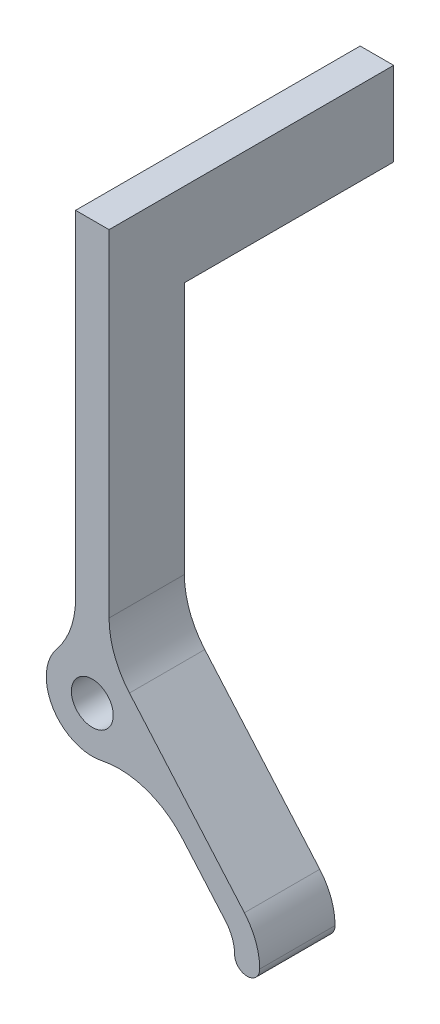
SolidWorks part; units mm, degrees
ref_plane "Front Plane" through (0, 0, 0) normal (0, 0, 1) x (1, 0, 0)
ref_plane "Top Plane" through (0, 0, 0) normal (0, 1, 0) x (1, 0, 0)
ref_plane "Right Plane" through (0, 0, 0) normal (1, 0, 0) x (0, 0, -1)
sketch "Sketch1" plane through (0, 0, 0) normal (0, 0, 1) x (1, 0, 0)
  line L0 (4.1588, 3.5992) -> (18.1711, -12.592)
  line L2 (15.9027, -14.5552) -> (5.0962, -2.0684)
  line L3 (2, 5.1235) -> (2, 50)
  line L4 (2, 50) -> (-2, 50)
  line L5 (-2, 50) -> (-2, 5.1235)
  circle A0 centre (0, 0) radius 2.5
  arc A1 (4.1588, 3.5992) -> (2, 5.1235) centre (0, 0) ccw
  arc A2 (-2, 5.1235) -> (5.0962, -2.0684) centre (0, 0) ccw
  arc A4 (15.9027, -14.5552) -> (17, -17.5) centre (12.5, -17.5) cw
  arc A5 (17, -17.5) -> (20, -17.5) centre (18.5, -17.5) ccw
  arc A6 (18.1711, -12.592) -> (20, -17.5) centre (12.5, -17.5) cw
  circle A7 centre (12.5, -17.5) radius 4.5 construction
  point P10 (0, 50)
  dimension "D1" = 5
  dimension "D2" = 5.5
  dimension "D8" = 17.5
  dimension "D5" = 1.5
  dimension "D9" = 9
  dimension "D3" = 3
  dimension "D4" = 12.5
  dimension "D6" = 4
  dimension "D7" = 50
extrude "Boss-Extrude1" add sketch "Sketch1" along normal blind 9
fillet "Fillet1" radius 10 3 edges at (5.0962, -2.0684, 4.5) (-2, 5.1235, 4.5) (2, 5.1235, 4.5)
sketch "Sketch2" plane through (0, 0, 0) normal (0, 0, -1) x (-1, 0, 0)
  line L0 (-2, 9.82) -> (-2, 50) construction
  line L1 (2, 50) -> (-2, 50)
  line L2 (2, 50) -> (2, 40)
  line L3 (2, 40) -> (-2, 40)
  line L4 (-2, 50) -> (-2, 40)
  dimension "D1" = 10
extrude "Boss-Extrude2" add sketch "Sketch2" along normal blind 25
